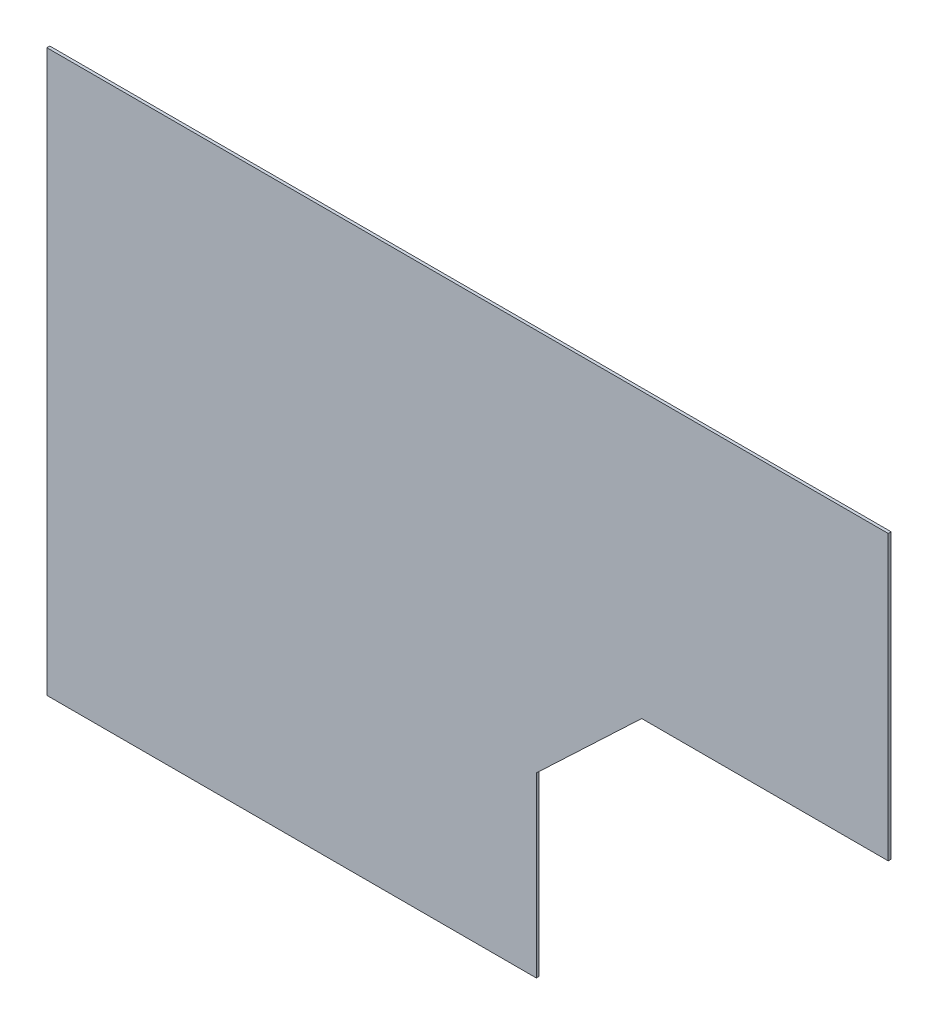
SolidWorks part; units mm, degrees
material "Acrylic (Medium-high impact)"
ref_plane "Front Plane" through (0, 0, 0) normal (0, 0, 1) x (1, 0, 0)
ref_plane "Top Plane" through (0, 0, 0) normal (0, 1, 0) x (1, 0, 0)
ref_plane "Right Plane" through (0, 0, 0) normal (1, 0, 0) x (0, 0, -1)
sketch "Sketch1" plane through (0, 0, 0) normal (0, 0, 1) x (1, 0, 0)
  line L1 (0, 0) -> (914.4, 0)
  line L2 (0, 0) -> (0, 609.6)
  line L3 (0, 609.6) -> (914.4, 609.6)
  line L4 (914.4, 0) -> (914.4, 609.6)
  dimension "D1" = 914.4
  dimension "D2" = 609.6
extrude "Boss-Extrude1" add sketch "Sketch1" along normal blind 3.175
sketch "Sketch2" plane through (0, 0, 3.175) normal (0, 0, 1) x (1, 0, 0)
  line L0 (531.9566, 0) -> (531.9566, 193.0018)
  line L1 (0, 0) -> (914.4, 0) construction
  line L2 (531.9566, 193.0018) -> (646.4488, 301.4326)
  line L3 (646.4488, 301.4326) -> (914.4, 301.4326)
  line L4 (914.4, 0) -> (914.4, 609.6) construction
  line L5 (914.4, 301.4326) -> (914.4, 0)
  line L6 (914.4, 0) -> (531.9566, 0)
extrude "Cut-Extrude1" cut sketch "Sketch2" against normal through all
sketch "Sketch4" [suppressed] plane through (0, 0, 4.7625) normal (0, 0, 1) x (1, 0, 0)
  line L0 (914.4, 301.4326) -> (914.4, 609.6)
  line L1 (914.4, 609.6) -> (0, 609.6)
  line L2 (0, 609.6) -> (0, 0)
  line L3 (0, 0) -> (531.9566, 0)
  line L5 (531.9566, 193.0018) -> (531.9566, 0)
  line L6 (646.4488, 301.4326) -> (531.9566, 193.0018)
  line L7 (914.4, 301.4326) -> (646.4488, 301.4326)
  line L8 (914.4, 0) -> (914.4, 301.4326)
  line L9 (531.9566, 0) -> (914.4, 0)
  line L10 (531.9566, 193.0018) -> (531.9566, 0)
  line L11 (646.4488, 301.4326) -> (531.9566, 193.0018)
  line L12 (914.4, 301.4326) -> (646.4488, 301.4326)
  dimension "D1" = 0
extrude "Cut-Extrude2" [suppressed] cut sketch "Sketch4" against normal blind 4.7625
equation "\"thick\"=0.125"
equation "\"D1@Boss-Extrude1\"=\"thick\""
